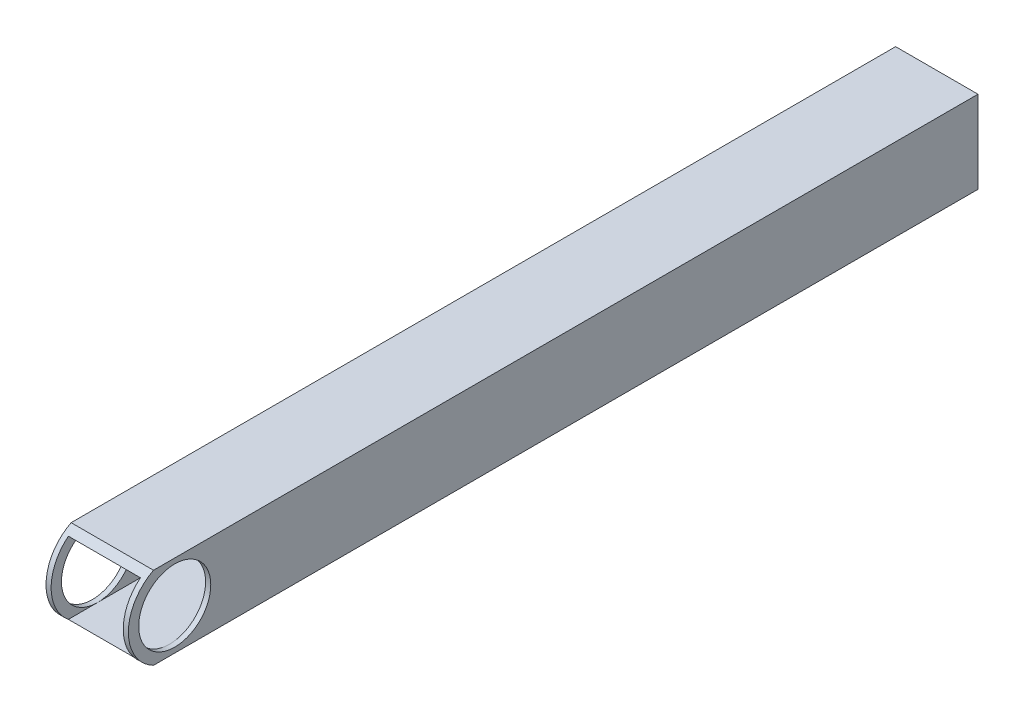
SolidWorks part; units mm, degrees
material "6061 Alloy"
ref_plane "Front Plane" through (0, 0, 0) normal (0, 0, 1) x (1, 0, 0)
ref_plane "Top Plane" through (0, 0, 0) normal (0, 1, 0) x (1, 0, 0)
ref_plane "Right Plane" through (0, 0, 0) normal (1, 0, 0) x (0, 0, -1)
sketch "Sketch1" plane through (0, 0, 0) normal (0, 0, 1) x (1, 0, 0)
  line L1 (12.7, -12.7) -> (-12.7, -12.7)
  line L2 (12.7, -12.7) -> (12.7, 12.7)
  line L3 (12.7, 12.7) -> (-12.7, 12.7)
  line L4 (-12.7, -12.7) -> (-12.7, 12.7)
  line L5 (12.7, -12.7) -> (-12.7, 12.7) construction
  line L6 (12.7, 12.7) -> (-12.7, -12.7) construction
  point P0 (0, 0)
  dimension "D1" = 25.4
extrude "Extrude-Thin1" add sketch "Sketch1" along normal mid plane 266.7 thin thin type one direction reverse wall 1.5875
sketch "Sketch2" plane through (12.7, 0, 0) normal (1, 0, 0) x (0, 0, -1)
  line L0 (-133.35, -12.7) -> (-133.35, 12.7) construction
  line L1 (-133.35, -12.7) -> (133.35, -12.7) construction
  circle A0 centre (-114.3, 0) radius 11.1125
  dimension "D1" = 22.225
  dimension "D2" = 19.05
  dimension "D3" = 12.7
extrude "Cut-Extrude1" cut sketch "Sketch2" against normal through all
sketch "Sketch3" plane through (12.7, 0, 0) normal (1, 0, 0) x (0, 0, -1)
  line L0 (-114.3, 14.2875) -> (-133.35, 14.2875)
  line L3 (-133.35, 14.2875) -> (-133.35, -12.7)
  line L4 (-133.35, -12.7) -> (-120.8454, -12.7)
  arc A0 (-114.3, 14.2875) -> (-120.8454, -12.7) centre (-114.3, 0) ccw
  circle A1 centre (-114.3, 0) radius 11.1125 construction
  point P2 (0, 0)
  point P3 (-330.3954, -12.3571)
  point P8 (-323.85, 14.2875)
  point P11 (0, 0)
  point P14 (0, 0)
  point P15 (0, 0)
  dimension "D1" = 3.175
extrude "Cut-Extrude2" cut sketch "Sketch3" against normal through all
